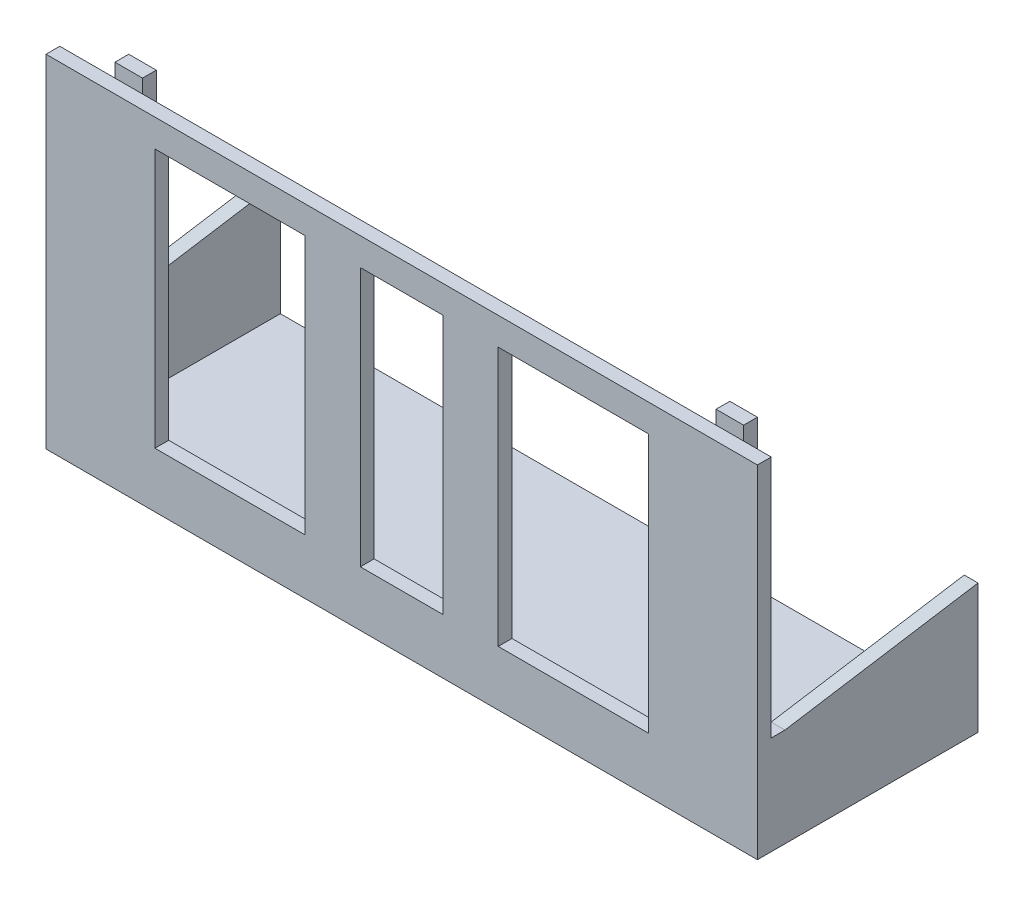
SolidWorks part; units mm, degrees
ref_plane "Спереди" through (0, 0, 0) normal (0, 0, 1) x (1, 0, 0)
ref_plane "Сверху" through (0, 0, 0) normal (0, 1, 0) x (1, 0, 0)
ref_plane "Справа" through (0, 0, 0) normal (1, 0, 0) x (0, 0, -1)
sketch "Эскиз2" plane through (0, 0, 0) normal (0, 0, 1) x (1, 0, 0)
  line L0 (-0.2, 19.6) -> (-0.2, 0.8)
  line L1 (-2.2, 21.6) -> (47.4, 21.6)
  line L2 (-2.2, 21.6) -> (-2.2, -1.2)
  line L3 (-2.2, -1.2) -> (47.4, -1.2)
  line L4 (47.4, 21.6) -> (47.4, -1.2)
  line L5 (-0.2, 0.8) -> (45.4, 0.8)
  line L6 (45.4, 19.6) -> (45.4, 0.8)
  line L7 (-0.2, 19.6) -> (45.4, 19.6)
  line L8 (22.6, 21.6) -> (22.6, -1.2) construction
  line L9 (15.6, 19.6) -> (19.6, 19.6)
  line L10 (15.6, 19.6) -> (15.6, 0.8)
  line L11 (15.6, 0.8) -> (19.6, 0.8)
  line L12 (19.6, 19.6) -> (19.6, 0.8)
  line L13 (29.6, 0.8) -> (25.6, 0.8)
  line L14 (25.6, 19.6) -> (25.6, 0.8)
  line L15 (29.6, 19.6) -> (25.6, 19.6)
  line L16 (29.6, 19.6) -> (29.6, 0.8)
  line L17 (45.4, 19.6) -> (40.5, 19.6)
  line L18 (-0.2, 0.8) -> (4.7, 0.8)
  line L19 (-0.2, 0.8) -> (-0.2, 19.6)
  line L20 (-0.2, 19.6) -> (4.7, 19.6)
  line L21 (4.7, 0.8) -> (4.7, 19.6)
  line L22 (40.5, 0.8) -> (40.5, 19.6)
  line L23 (45.4, 0.8) -> (40.5, 0.8)
  line L24 (45.4, 0.8) -> (45.4, 19.6)
  arc A0 (38, 8.7) -> (38, 11.7) centre (38, 10.2) ccw construction
  line M20 (47.4, 16.45) -> (47.4, 21.6)
  line M21 (47.4, 21.6) -> (-2.2, 21.6)
  line M22 (-2.2, 21.6) -> (-2.2, 16.45)
  line M26 (-2.2, 3.95) -> (-2.2, -1.2)
  line M27 (-2.2, -1.2) -> (47.4, -1.2)
  line M28 (47.4, -1.2) -> (47.4, 3.95)
  arc M32 (38, 11.7) -> (38, 8.7) centre (38, 10.2) cw
  dimension "D2" = 4
  dimension "D3" = 6
  dimension "D4" = 2.5
  dimension "D1" = 2
extrude "Бобышка-Вытянуть1" add sketch "Эскиз2" along normal blind 1 contours L8 L1 L2 L5 L0 L7 M22 M26 M27 | L12 L7 L10 L5 | L8 L7 L6 L5 L3 L4 M21 M28 M20 | L16 L7 L14 L5 | L5 L21 L7 L0 | L22 L5 L6 L7 M32 region at (2.25, 10.2, 0) region at (-0.5369, 10.2, 0) region at (17.6, 10.2, 0) region at (22.9369, 20.6, 0) region at (27.6, 10.2, 0) region at (42.95, 10.2, 0)
sketch "Эскиз4" plane through (0, -1.2, 0) normal (0, -1, 0) x (1, 0, 0)
  line L1 (-2.2, 0) -> (47.4, 0)
  line L2 (-2.2, 0) -> (-2.2, 1)
  line L3 (-2.2, 1) -> (47.4, 1)
  line L4 (47.4, 0) -> (47.4, 1)
extrude "Бобышка-Вытянуть2" add sketch "Эскиз4" along normal blind 2
sketch "Эскиз5" plane through (0, 0, 0) normal (0, 0, -1) x (-1, 0, 0)
  line L0 (-47.4, -3.2) -> (-47.4, 21.6) construction
  line L1 (2.2, -3.2) -> (-47.4, -3.2)
  line L2 (2.2, -3.2) -> (2.2, -2.2)
  line L3 (2.2, -2.2) -> (-47.4, -2.2)
  line L4 (-47.4, -3.2) -> (-47.4, -2.2)
  dimension "D1" = 1
extrude "Бобышка-Вытянуть3" add sketch "Эскиз5" along normal blind 15
sketch "Эскиз6" plane through (-2.2, 0, 0) normal (-1, 0, 0) x (0, 0, 1)
  line L0 (0, 3.95) -> (-1, 3.95)
  line L1 (0, 21.6) -> (0, -2.2) construction
  line L2 (-1, 3.95) -> (0, 3.95) construction
  line L3 (-1, 3.95) -> (-15, 6.1847)
  line L4 (-19.7945, 6.95) -> (-1, 3.95) construction
  line L5 (-15, 6.1847) -> (-15, -3.2)
  line L6 (-15, -3.2) -> (1, -3.2)
  line L7 (1, -3.2) -> (1, 3.95)
  line L8 (1, 21.6) -> (1, -3.2) construction
  line L9 (1, 3.95) -> (0, 3.95)
  line L11 (1, 3.95) -> (0, 3.95)
  line L12 (1, 3.95) -> (1, 21.6)
  line L13 (1, 21.6) -> (0, 21.6)
  line L14 (0, 3.95) -> (0, 21.6)
  line M7 (0, 21.6) -> (0, -2.2)
  line M8 (0, -2.2) -> (-15, -2.2)
  line M9 (-15, -2.2) -> (-15, -3.2)
  line M10 (-15, -3.2) -> (1, -3.2)
  line M11 (1, -3.2) -> (1, 21.6)
  line M12 (1, 21.6) -> (0, 21.6)
extrude "Бобышка-Вытянуть6" add sketch "Эскиз6" along normal blind 1 contours L9 M11 M12 M7 | L9 M11 M7 M8 M9 M10 | L3 L5 L0 M8 M7 region at (-2.2, 1.4288, -7.9108) region at (-2.2, 12.775, 0.5) region at (-2.2, 3.7748, 0.5)
ref_plane "Плоскость1" through (22.6, 0, 0) normal (-1, 0, 0) x (0, 0, 1)
mirror "Зеркальное отражение1" about plane through (22.6, 0, 0) normal (-1, 0, 0) of "Бобышка-Вытянуть6"
sketch "Эскиз7" plane through (0, 0, 0) normal (0, 0, -1) x (-1, 0, 0)
  line L0 (-22.6, 21.6) -> (-22.6, -3.2) construction
  line L1 (-48.4, 21.6) -> (3.2, 21.6) construction
  line L2 (-48.4, -3.2) -> (3.2, -3.2) construction
  line L3 (-48.4, 21.6) -> (-48.4, 3.95) construction
  line L4 (-45.4, 19.6) -> (-43.4, 19.6)
  line L5 (-45.4, 19.6) -> (-45.4, 17.6)
  line L6 (-45.4, 17.6) -> (-43.4, 17.6)
  line L7 (-43.4, 19.6) -> (-43.4, 17.6)
  line L8 (-1.8, 19.6) -> (-1.8, 17.6)
  line L9 (0.2, 17.6) -> (-1.8, 17.6)
  line L10 (0.2, 19.6) -> (0.2, 17.6)
  line L11 (0.2, 19.6) -> (-1.8, 19.6)
  dimension "D1" = 2
  dimension "D2" = 3
  dimension "D3" = 2
extrude "Бобышка-Вытянуть7" add sketch "Эскиз7" along normal blind 2
sketch "Эскиз8" plane through (0, 19.6, 0) normal (0, 1, 0) x (1, 0, 0)
  line L0 (1.8, 2) -> (1.8, 0) construction
  line L1 (-0.2, 2) -> (1.8, 2)
  line L2 (-0.2, 2) -> (-0.2, 1)
  line L3 (-0.2, 1) -> (1.8, 1)
  line L4 (1.8, 2) -> (1.8, 1)
  line L5 (22.6, -1) -> (22.6, 0) construction
  line L6 (48.4, -1) -> (-3.2, -1) construction
  line L7 (48.4, 0) -> (-3.2, 0) construction
  line L8 (45.4, 2) -> (45.4, 0) construction
  line L9 (45.4, 2) -> (43.4, 2)
  line L10 (45.4, 2) -> (45.4, 1)
  line L11 (45.4, 1) -> (43.4, 1)
  line L12 (43.4, 2) -> (43.4, 1)
  line L13 (43.4, 2) -> (43.4, 0) construction
  line L14 (43.4, 2) -> (45.4, 2) construction
extrude "Бобышка-Вытянуть8" add sketch "Эскиз8" along normal up to surface (2 mm away) up to face at (22.6, 21.6, 0.5)
chamfer "Фаска1" distance 2 angle 45 2 edges at (0.8, 17.6, -2) (44.4, 17.6, -2)
